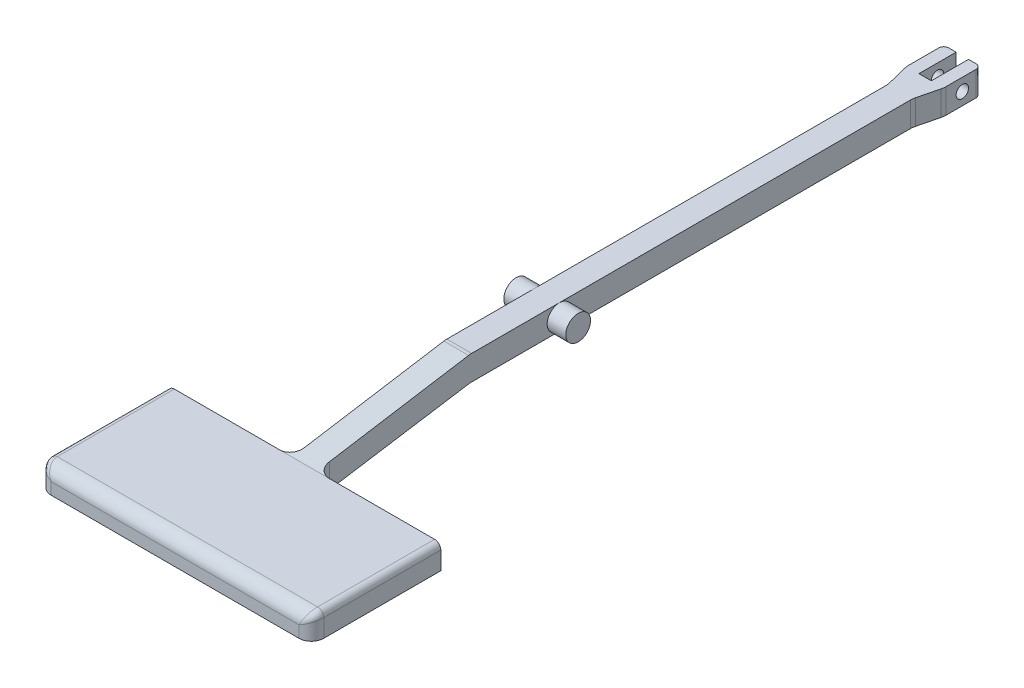
SolidWorks part; units mm, degrees
material "Plain Carbon Steel"
ref_plane "Front Plane" through (0, 0, 0) normal (0, 0, 1) x (1, 0, 0)
ref_plane "Top Plane" through (0, 0, 0) normal (0, 1, 0) x (1, 0, 0)
ref_plane "Right Plane" through (0, 0, 0) normal (1, 0, 0) x (0, 0, -1)
sketch "Sketch1" plane through (0, 0, 0) normal (0, 1, 0) x (1, 0, 0)
  line L0 (10.16, 139.7) -> (0, 139.7) construction
  line L1 (0, 0) -> (10.16, 0)
  line L2 (0, 0) -> (0, 279.4)
  line L3 (0, 279.4) -> (10.16, 279.4)
  line L4 (10.16, 0) -> (10.16, 279.4)
  dimension "D1" = 279.4
  dimension "D2" = 10.16
extrude "Boss-Extrude1" add sketch "Sketch1" along normal blind 10.16
sketch "Sketch2" plane through (10.16, 0, 0) normal (1, 0, 0) x (0, 0, -1)
  line L4 (0, 0) -> (279.4, 0)
  line L5 (279.4, 0) -> (279.4, 10.16)
  line L6 (279.4, 10.16) -> (0, 10.16)
  line L7 (0, 10.16) -> (0, 0)
  line L8 (0, 0) -> (279.4, 0)
  line L9 (279.4, 0) -> (279.4, 10.16)
  line L10 (279.4, 10.16) -> (0, 10.16)
  line L11 (0, 10.16) -> (0, 0)
  circle A0 centre (139.7, 5.08) radius 5.08
  dimension "D2" = 10.16
  dimension "D3" = 139.7
  dimension "D1" = 0
extrude "Boss-Extrude2" add sketch "Sketch2" along normal blind 7.62 contours A0 region at (10.16, 5.08, -139.7)
sketch "Sketch4" plane through (17.78, 0, 0) normal (1, 0, 0) x (0, 0, -1)
  circle A1 centre (139.7, 5.08) radius 5.08
  circle A2 centre (139.7, 5.08) radius 5.08
  dimension "D1" = 0
extrude "Boss-Extrude3" add sketch "Sketch4" against normal blind 25.4
sketch "Sketch5" plane through (0, 10.16, 0) normal (0, 1, 0) x (1, 0, 0)
  line L0 (0, 279.4) -> (0, 284.48)
  line L1 (0, 284.48) -> (-2.54, 294.64)
  line L2 (-2.54, 294.64) -> (-2.54, 309.88)
  line L3 (-2.54, 309.88) -> (2.54, 309.88)
  line L4 (2.54, 309.88) -> (2.54, 294.64)
  line L5 (2.54, 294.64) -> (7.62, 294.64)
  line L6 (0, 279.4) -> (0, 139.7)
  line L7 (0, 139.7) -> (0, 0)
  line L8 (0, 0) -> (10.16, 0)
  line L9 (10.16, 0) -> (10.16, 139.7)
  line L10 (10.16, 139.7) -> (10.16, 279.4)
  line L11 (10.16, 279.4) -> (0, 279.4)
  line L12 (0, 279.4) -> (0, 139.7)
  line L13 (0, 139.7) -> (0, 0)
  line L14 (0, 0) -> (10.16, 0)
  line L15 (10.16, 0) -> (10.16, 139.7)
  line L16 (10.16, 139.7) -> (10.16, 279.4)
  line L17 (10.16, 279.4) -> (0, 279.4)
  line L18 (5.08, 279.4) -> (5.08, 299.8167) construction
  line L19 (7.62, 309.88) -> (7.62, 294.64)
  line L20 (12.7, 309.88) -> (7.62, 309.88)
  line L21 (12.7, 294.64) -> (12.7, 309.88)
  line L22 (10.16, 284.48) -> (12.7, 294.64)
  line L23 (10.16, 279.4) -> (10.16, 284.48)
  point P15 (5.08, 294.64)
  line M20 (10.16, 279.4) -> (0, 279.4)
  dimension "D2" = 2.54
  dimension "D3" = 7.62
  dimension "D4" = 30.48
  dimension "D5" = 15.24
  dimension "D6" = 5.08
  dimension "D7" = 15.24
  dimension "D1" = 0
extrude "Boss-Extrude4" add sketch "Sketch5" against normal blind 10.16 contours L17 L18 L5 L4 L3 L2 L1 L0 | L18 L23 L22 L21 L20 L19 L5 M20 region at (1.1072, 10.16, -294.3795) region at (9.0528, 10.16, -294.3795)
sketch "Sketch6" plane through (12.7, 0, 0) normal (1, 0, 0) x (0, 0, -1)
  line L4 (309.88, 10.16) -> (294.64, 10.16)
  line L5 (294.64, 10.16) -> (294.64, 0)
  line L6 (294.64, 0) -> (309.88, 0)
  line L7 (309.88, 0) -> (309.88, 10.16)
  line L8 (309.88, 10.16) -> (294.64, 10.16)
  line L9 (294.64, 10.16) -> (294.64, 0)
  line L10 (294.64, 0) -> (309.88, 0)
  line L11 (309.88, 0) -> (309.88, 10.16)
  circle A0 centre (302.26, 5.08) radius 2.54
  dimension "D2" = 5.08
  dimension "D3" = 7.62
  dimension "D4" = 5.08
  dimension "D1" = 0
extrude "Cut-Extrude1" cut sketch "Sketch6" against normal through all both and the other way through all contours A0
ref_plane "Plane1" through (10.16, 10.16, 0) normal (0, 0, -1) x (-1, 0, 0)
sketch "Sketch8" plane through (10.16, 0, 0) normal (1, 0, 0) x (0, 0, -1)
  line L3 (40.2172, 10.16) -> (0, 0)
  line L4 (0, 10.16) -> (40.2172, 10.16)
  line L5 (0, 10.16) -> (139.7, 10.16) construction
  line L6 (139.7, 10.16) -> (0, 10.16)
  line L7 (0, 10.16) -> (0, 0)
  line L8 (0, 0) -> (139.7, 0)
  line L9 (139.7, 10.16) -> (0, 10.16)
  line L10 (0, 10.16) -> (0, 0)
  line L11 (0, 0) -> (139.7, 0)
  arc A2 (139.7, 10.16) -> (139.7, 0) centre (139.7, 5.08) ccw
  arc A3 (139.7, 10.16) -> (139.7, 0) centre (139.7, 5.08) ccw
  line M6 (139.7, 10.16) -> (0, 10.16)
  line M7 (0, 10.16) -> (0, 0)
  dimension "D1" = 0
extrude "Cut-Extrude2" cut sketch "Sketch8" against normal through all both and the other way through all contours L3 M6 M7 region at (10.16, 6.7733, -13.4057)
sketch "Sketch9" plane through (10.16, 0, 0) normal (1, 0, 0) x (0, 0, -1)
  line L0 (40.2172, 10.16) -> (40.2172, 0)
  line L1 (40.2172, 0) -> (2.3, -9.8963)
  line L2 (2.3, -9.8963) -> (0, 0)
  line L3 (40.2172, 10.16) -> (0, 0)
  line L4 (0, 0) -> (139.7, 0)
  line L5 (139.7, 10.16) -> (40.2172, 10.16)
  line L6 (40.2172, 10.16) -> (0, 0)
  line L7 (0, 0) -> (139.7, 0)
  line L8 (139.7, 10.16) -> (40.2172, 10.16)
  arc A1 (139.7, 10.16) -> (139.7, 0) centre (139.7, 5.08) ccw
  arc A2 (139.7, 10.16) -> (139.7, 0) centre (139.7, 5.08) ccw
  line M6 (0, 0) -> (139.7, 0)
  dimension "D2" = 10.16
  dimension "D1" = 0
extrude "Boss-Extrude5" add sketch "Sketch9" against normal blind 10.16 contours L2 L1 M6 region at (10.16, -3.2988, -14.1724)
sketch "Sketch10" plane through (10.16, 0, 0) normal (1, 0, 0) x (0, 0, -1)
  line L0 (0, 0) -> (-32.5546, 0)
  line L1 (-32.5546, 0) -> (-32.5546, -9.8963)
  line L2 (-32.5546, -9.8963) -> (2.3, -9.8963)
  line L5 (40.2172, 10.16) -> (0, 0)
  line L6 (0, 0) -> (2.3, -9.8963)
  line L7 (2.3, -9.8963) -> (40.2172, 0)
  line L8 (40.2172, 0) -> (139.7, 0)
  line L9 (139.7, 10.16) -> (40.2172, 10.16)
  line L10 (40.2172, 10.16) -> (0, 0)
  line L11 (0, 0) -> (2.3, -9.8963)
  line L12 (2.3, -9.8963) -> (40.2172, 0)
  line L13 (40.2172, 0) -> (139.7, 0)
  line L14 (139.7, 10.16) -> (40.2172, 10.16)
  arc A1 (139.7, 10.16) -> (139.7, 0) centre (139.7, 5.08) ccw
  arc A2 (139.7, 10.16) -> (139.7, 0) centre (139.7, 5.08) ccw
  line M8 (0, 0) -> (2.3, -9.8963)
  dimension "D1" = 0
extrude "Boss-Extrude6" add sketch "Sketch10" against normal blind 35.56 contours L1 L2 L0 M8 region at (10.16, -5.0044, 15.6958)
sketch "Sketch11" plane through (-25.4, 0, 0) normal (-1, 0, 0) x (0, 0, 1)
  line L4 (32.5546, -9.8963) -> (32.5546, 0)
  line L5 (32.5546, 0) -> (0, 0)
  line L6 (0, 0) -> (-2.3, -9.8963)
  line L7 (-2.3, -9.8963) -> (32.5546, -9.8963)
  line L8 (32.5546, -9.8963) -> (32.5546, 0)
  line L9 (32.5546, 0) -> (0, 0)
  line L10 (0, 0) -> (-2.3, -9.8963)
  line L11 (-2.3, -9.8963) -> (32.5546, -9.8963)
  dimension "D1" = 0
extrude "Boss-Extrude7" add sketch "Sketch11" against normal blind 60.96
sketch "Sketch12" plane through (10.16, 0, 0) normal (1, 0, 0) x (0, 0, -1)
  line L0 (103.0312, 10.16) -> (40.2172, 0)
  line L1 (40.2172, 10.16) -> (139.7, 10.16) construction
  line L2 (40.2172, 0) -> (0, 0)
  line L3 (0, 0) -> (2.3, -9.8963)
  line L4 (2.3, -9.8963) -> (40.2172, -9.8963)
  line L5 (40.2172, -9.8963) -> (103.0312, 0)
  line L6 (40.2172, 0) -> (139.7, 0) construction
  line L7 (103.0312, 0) -> (103.0312, 10.16)
extrude "Boss-Extrude8" add sketch "Sketch12" against normal blind 10.16
sketch "Sketch13" plane through (10.16, 0, 0) normal (1, 0, 0) x (0, 0, -1)
  line L0 (0, 0) -> (40.2172, 0)
  line L1 (40.2172, 0) -> (103.0312, 10.16)
  line L2 (103.0312, 10.16) -> (103.0312, 22.6781)
  line L3 (103.0312, 22.6781) -> (-2.8307, 14.7224)
  line L4 (-2.8307, 14.7224) -> (0, 0)
  line L6 (40.2172, -9.8963) -> (103.0312, 0)
  line L7 (103.0312, 0) -> (139.7, 0)
  line L8 (139.7, 10.16) -> (40.2172, 10.16)
  line L9 (40.2172, 10.16) -> (0, 0)
  line L10 (40.2172, -9.8963) -> (103.0312, 0)
  line L11 (2.3, -9.8963) -> (40.2172, -9.8963)
  line L12 (0, 0) -> (2.3, -9.8963)
  line L13 (103.0312, 0) -> (139.7, 0)
  line L14 (139.7, 10.16) -> (40.2172, 10.16)
  line L15 (40.2172, 10.16) -> (0, 0)
  line L16 (0, 0) -> (2.3, -9.8963)
  line L17 (2.3, -9.8963) -> (40.2172, -9.8963)
  arc A1 (139.7, 10.16) -> (139.7, 0) centre (139.7, 5.08) ccw
  arc A2 (139.7, 10.16) -> (139.7, 0) centre (139.7, 5.08) ccw
  line M11 (139.7, 10.16) -> (40.2172, 10.16)
  line M12 (40.2172, 10.16) -> (0, 0)
  dimension "D1" = 0
extrude "Cut-Extrude3" cut sketch "Sketch13" against normal blind 10.16 contours L0 L1 M11 M12 region at (10.16, 5.4514, -47.7495)
sketch "Sketch14" plane through (35.56, 0, 0) normal (1, 0, 0) x (0, 0, -1)
  line L4 (-32.5546, -9.8963) -> (2.3, -9.8963)
  line L5 (2.3, -9.8963) -> (0, 0)
  line L6 (0, 0) -> (-32.5546, 0)
  line L7 (-32.5546, 0) -> (-32.5546, -9.8963)
  line L8 (-32.5546, -9.8963) -> (2.3, -9.8963)
  line L9 (2.3, -9.8963) -> (0, 0)
  line L10 (0, 0) -> (-32.5546, 0)
  line L11 (-32.5546, 0) -> (-32.5546, -9.8963)
  dimension "D1" = 0
extrude "Cut-Extrude4" cut sketch "Sketch14" against normal through all both and the other way through all
sketch "Sketch15" plane through (10.16, 0, 0) normal (1, 0, 0) x (0, 0, -1)
  line L0 (0, 0) -> (10.1601, 0)
  line L1 (10.1601, 0) -> (10.1601, -9.8963)
  line L2 (10.1601, -9.8963) -> (2.3, -9.8963)
  line L7 (103.0312, 10.16) -> (40.2172, 0)
  line L8 (40.2172, 0) -> (0, 0)
  line L9 (0, 0) -> (2.3, -9.8963)
  line L10 (2.3, -9.8963) -> (40.2172, -9.8963)
  line L11 (40.2172, -9.8963) -> (103.0312, 0)
  line L12 (103.0312, 0) -> (139.7, 0)
  line L13 (139.7, 10.16) -> (103.0312, 10.16)
  line L14 (103.0312, 10.16) -> (40.2172, 0)
  line L15 (40.2172, 0) -> (0, 0)
  line L16 (0, 0) -> (2.3, -9.8963)
  line L17 (2.3, -9.8963) -> (40.2172, -9.8963)
  line L18 (40.2172, -9.8963) -> (103.0312, 0)
  line L19 (103.0312, 0) -> (139.7, 0)
  line L20 (139.7, 10.16) -> (103.0312, 10.16)
  arc A1 (139.7, 10.16) -> (139.7, 0) centre (139.7, 5.08) ccw
  arc A2 (139.7, 10.16) -> (139.7, 0) centre (139.7, 5.08) ccw
  line M10 (40.2172, 0) -> (0, 0)
  line M11 (0, 0) -> (2.3, -9.8963)
  line M12 (2.3, -9.8963) -> (40.2172, -9.8963)
  dimension "D1" = 0
extrude "Cut-Extrude5" cut sketch "Sketch15" against normal through all both and the other way through all contours L1 M10 M11 M12 region at (10.16, -4.7376, -5.6306)
sketch "Sketch16" plane through (10.16, 0, 0) normal (1, 0, 0) x (0, 0, -1)
  line L0 (40.2172, 0) -> (40.2172, -9.8963)
  line L1 (10.1601, -9.8963) -> (10.1601, 0)
  line L7 (10.1601, 0) -> (10.1601, -9.8963)
  line L8 (10.1601, -9.8963) -> (40.2172, -9.8963)
  line L9 (40.2172, -9.8963) -> (103.0312, 0)
  line L10 (103.0312, 0) -> (139.7, 0)
  line L11 (139.7, 10.16) -> (103.0312, 10.16)
  line L12 (103.0312, 10.16) -> (40.2172, 0)
  line L13 (40.2172, 0) -> (10.1601, 0)
  line L14 (10.1601, 0) -> (10.1601, -9.8963)
  line L15 (10.1601, -9.8963) -> (40.2172, -9.8963)
  line L16 (40.2172, -9.8963) -> (103.0312, 0)
  line L17 (103.0312, 0) -> (139.7, 0)
  line L18 (139.7, 10.16) -> (103.0312, 10.16)
  line L19 (103.0312, 10.16) -> (40.2172, 0)
  line L20 (40.2172, 0) -> (10.1601, 0)
  arc A1 (139.7, 10.16) -> (139.7, 0) centre (139.7, 5.08) ccw
  arc A2 (139.7, 10.16) -> (139.7, 0) centre (139.7, 5.08) ccw
  dimension "D1" = 0
sketch "Sketch17" plane through (0, 0, 0) normal (-1, 0, 0) x (0, 0, 1)
  line L0 (-40.2172, 0) -> (-40.2172, -9.8963)
  line L1 (-10.1601, -9.8963) -> (-10.1601, 0)
  line L7 (-10.1601, -9.8963) -> (-10.1601, 0)
  line L8 (-10.1601, 0) -> (-40.2172, 0)
  line L9 (-40.2172, 0) -> (-103.0312, 10.16)
  line L10 (-103.0312, 10.16) -> (-139.7, 10.16)
  line L11 (-139.7, 0) -> (-103.0312, 0)
  line L12 (-103.0312, 0) -> (-40.2172, -9.8963)
  line L13 (-40.2172, -9.8963) -> (-10.1601, -9.8963)
  line L14 (-10.1601, -9.8963) -> (-10.1601, 0)
  line L15 (-10.1601, 0) -> (-40.2172, 0)
  line L16 (-40.2172, 0) -> (-103.0312, 10.16)
  line L17 (-103.0312, 10.16) -> (-139.7, 10.16)
  line L18 (-139.7, 0) -> (-103.0312, 0)
  line L19 (-103.0312, 0) -> (-40.2172, -9.8963)
  line L20 (-40.2172, -9.8963) -> (-10.1601, -9.8963)
  arc A1 (-139.7, 0) -> (-139.7, 10.16) centre (-139.7, 5.08) ccw
  arc A2 (-139.7, 0) -> (-139.7, 10.16) centre (-139.7, 5.08) ccw
  line M9 (-10.1601, -9.8963) -> (-10.1601, 0)
  line M10 (-10.1601, 0) -> (-40.2172, 0)
  line M16 (-40.2172, -9.8963) -> (-10.1601, -9.8963)
  dimension "D1" = 0
extrude "Boss-Extrude10" add sketch "Sketch17" along normal blind 50.8 contours L0 M10 M16 M9 region at (0, -4.9481, -25.1886)
fillet "Fillet4" radius 7.62 1 edges at (5.08, 0, -103.0312)
fillet "Fillet5" radius 7.62 1 edges at (5.08, 10.16, -103.0312)
fillet "Fillet6" radius 7.62 1 edges at (12.7, 5.08, -294.64)
fillet "Fillet7" radius 7.62 1 edges at (10.16, 5.08, -284.48)
fillet "Fillet8" radius 7.62 1 edges at (-2.54, 5.08, -294.64)
fillet "Fillet9" radius 7.62 1 edges at (0, 5.08, -284.48)
fillet "Fillet10" radius 2.032 1 edges at (-2.54, 5.08, -309.88)
fillet "Fillet11" radius 2.032 1 edges at (12.7, 5.08, -309.88)
sketch "Sketch18" plane through (10.16, 0, 0) normal (1, 0, 0) x (0, 0, -1)
  line L0 (40.2172, 0) -> (-12.8402, 0)
  line L1 (-12.8402, 0) -> (-12.8402, -9.8963)
  line L2 (-12.8402, -9.8963) -> (40.2172, -9.8963)
  line L3 (40.2172, 0) -> (40.2172, -9.8963)
  line L7 (139.7, 10.16) -> (103.6435, 10.16)
  line L8 (102.4268, 10.0622) -> (40.2172, 0)
  line L9 (40.2172, 0) -> (10.1601, 0)
  line L10 (10.1601, 0) -> (10.1601, -9.8963)
  line L11 (10.1601, -9.8963) -> (40.2172, -9.8963)
  line L12 (40.2172, -9.8963) -> (102.4419, -0.0928)
  line L13 (103.6278, 0) -> (139.7, 0)
  line L14 (139.7, 10.16) -> (103.6435, 10.16)
  line L15 (102.4268, 10.0622) -> (40.2172, 0)
  line L16 (40.2172, 0) -> (10.1601, 0)
  line L17 (10.1601, 0) -> (10.1601, -9.8963)
  line L18 (10.1601, -9.8963) -> (40.2172, -9.8963)
  line L19 (40.2172, -9.8963) -> (102.4419, -0.0928)
  line L20 (103.6278, 0) -> (139.7, 0)
  arc A3 (103.6435, 10.16) -> (102.4268, 10.0622) centre (103.6435, 2.54) ccw
  arc A4 (103.6278, 0) -> (102.4419, -0.0928) centre (103.6278, -7.62) ccw
  arc A5 (139.7, 10.16) -> (139.7, 0) centre (139.7, 5.08) ccw
  arc A6 (103.6435, 10.16) -> (102.4268, 10.0622) centre (103.6435, 2.54) ccw
  arc A7 (103.6278, 0) -> (102.4419, -0.0928) centre (103.6278, -7.62) ccw
  arc A8 (139.7, 10.16) -> (139.7, 0) centre (139.7, 5.08) ccw
  line M14 (40.2172, 0) -> (10.1601, 0)
  line M15 (10.1601, 0) -> (10.1601, -9.8963)
  line M16 (10.1601, -9.8963) -> (40.2172, -9.8963)
  dimension "D1" = 0
extrude "Boss-Extrude11" add sketch "Sketch18" along normal blind 50.8 contours L1 L2 L0 M15 | L3 M14 M15 M16 region at (10.16, -4.9481, -25.1886) region at (10.16, -4.9481, 1.3401)
sketch "Sketch19" plane through (10.16, 0, 0) normal (-1, 0, 0) x (0, 0, 1)
  line L4 (-10.1601, 0) -> (-10.1601, -9.8963)
  line L5 (-10.1601, -9.8963) -> (12.8402, -9.8963)
  line L6 (12.8402, -9.8963) -> (12.8402, 0)
  line L7 (12.8402, 0) -> (-10.1601, 0)
  line L8 (-10.1601, 0) -> (-10.1601, -9.8963)
  line L9 (-10.1601, -9.8963) -> (12.8402, -9.8963)
  line L10 (12.8402, -9.8963) -> (12.8402, 0)
  line L11 (12.8402, 0) -> (-10.1601, 0)
  dimension "D1" = 0
extrude "Boss-Extrude12" add sketch "Sketch19" along normal blind 60.96
fillet "Fillet13" radius 2.54 1 edges at (-50.8, 0, -13.6885)
fillet "Fillet14" radius 2.54 1 edges at (60.96, 0, -13.6885)
fillet "Fillet15" radius 5.08 5 edges at (60.96, -6.2181, 12.8402) (60.2161, -0.7439, 12.8402) (-50.8, -6.2181, 12.8402) (-50.0561, -0.7439, 12.8402) (5.08, 0, 12.8402)
fillet "Fillet16" radius 5.08 1 edges at (10.16, -4.9481, -40.2172)
fillet "Fillet17" radius 5.08 1 edges at (0, -4.9481, -40.2172)
